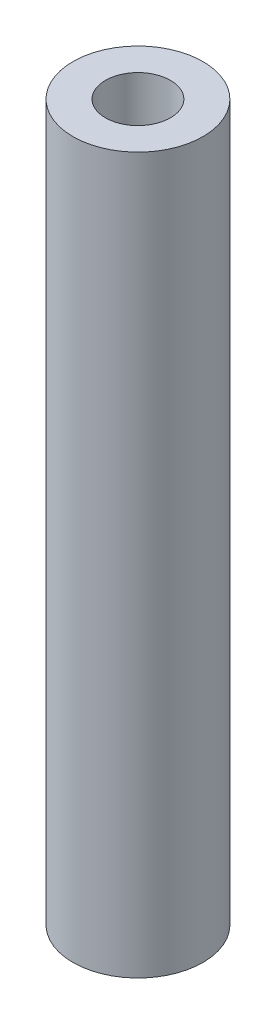
SolidWorks part; units mm, degrees
ref_plane "Front Plane" through (0, 0, 0) normal (0, 0, 1) x (1, 0, 0)
ref_plane "Top Plane" through (0, 0, 0) normal (0, 1, 0) x (1, 0, 0)
ref_plane "Right Plane" through (0, 0, 0) normal (1, 0, 0) x (0, 0, -1)
sketch "Sketch1" plane through (0, 0, 0) normal (0, 1, 0) x (1, 0, 0)
  circle A0 centre (0, 0) radius 3
  dimension "D1" = 6
extrude "Boss-Extrude1" add sketch "Sketch1" along normal blind 33
hole_wizard "Ø3.0mm Dowel Hole1" positions "3DSketch1" profile "Sketch2" hole size "Ø3.0" standard "DIN" end condition through all
sketch3d "3DSketch1"
  line L0 (0, 33, 0) -> (0, 0, 0) construction
  point P0 (0, 33, 0)
sketch "Sketch2" plane through (0, 33, 0) normal (1, 0, 0) x (0, 0, 1)
  line L0 (0, 0) -> (0, 33)
  line L1 (0, 33) -> (1.5, 33)
  line L2 (1.5, 33) -> (1.5, 0)
  line L5 (1.5, 0) -> (0, 0)
  line L11 (0, -6.35) -> (0, 107.95) construction
  dimension "Thru Hole Dia." = 3
  dimension "Thru Hole Depth" = 33
